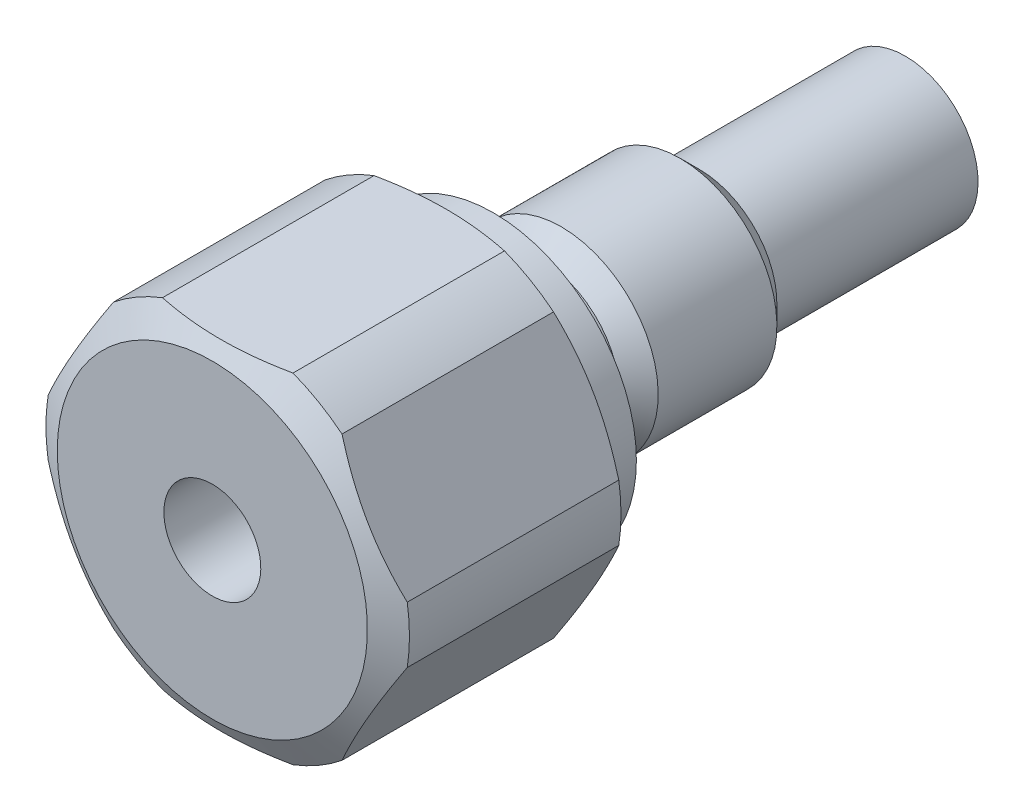
SolidWorks part; units mm, degrees
material "AISI 316 Annealed Stainless Steel Bar (SS)"
ref_plane "Front Plane" through (0, 0, 0) normal (0, 0, 1) x (1, 0, 0)
ref_plane "Top Plane" through (0, 0, 0) normal (0, 1, 0) x (1, 0, 0)
ref_plane "Right Plane" through (0, 0, 0) normal (1, 0, 0) x (0, 0, -1)
ref_axis "CENTER" through (0, 0, 55) along (0, 0, -1)
sketch "Sketch1" plane through (0, 0, 0) normal (1, 0, 0) x (0, 0, -1)
  line L0 (105.3808, 0) -> (-49894.6192, 0) construction
  line L1 (-55, 0) -> (55, 0) construction
  line L2 (0, 2) -> (0, 3)
  line L3 (0, 3) -> (-8.5, 3)
  line L4 (-17, 3.2) -> (-17, 5.9)
  line L5 (-17, 5.9) -> (-18.6, 5.9)
  line L6 (-18.6, 5.9) -> (-18.6, 7)
  line L7 (-18.6, 7) -> (-28.6, 7)
  line L8 (-28.6, 7) -> (-28.6, 2)
  line L9 (-28.6, 2) -> (0, 2)
  line L10 (-17, 3.2) -> (-15, 3.2)
  line L11 (-15, 3.2) -> (-14.2, 4)
  line L12 (-14.2, 4) -> (-9.3, 4)
  line L13 (-9.3, 4) -> (-8.5, 3.2)
  line L14 (-8.5, 3.2) -> (-8.5, 3)
  dimension "D1" = 4
  dimension "D2" = 1
  dimension "D3" = 11.8
  dimension "D4" = 8
  dimension "D5" = 6.4
  dimension "D6" = 8.5
  dimension "D7" = 45
  dimension "D8" = 2
  dimension "D9" = 1.6
  dimension "D10" = 14
  dimension "D11" = 10
  dimension "D12" = 17
revolve "Main Base" add sketch "Sketch1" angle 360 about L0
sketch "Sketch3" plane through (0, 0, 28.6) normal (0, 0, 1) x (1, 0, 0)
  line L1 (8.0829, 0) -> (4.0415, 7)
  line L2 (4.0415, 7) -> (-4.0415, 7)
  line L3 (-4.0415, 7) -> (-8.0829, 0)
  line L4 (-8.0829, 0) -> (-4.0415, -7)
  line L5 (-4.0415, -7) -> (4.0415, -7)
  line L6 (4.0415, -7) -> (8.0829, 0)
  circle A0 centre (0, 0) radius 7 construction
  circle A1 centre (0, 0) radius 7 construction
  circle A2 centre (0, 0) radius 2 construction
  circle A3 centre (0, 0) radius 2
extrude "Hex Head" add sketch "Sketch3" against normal up to surface (10 mm away) up to face at (0, 7, 18.6)
sketch "Sketch5" plane through (0, 0, 0) normal (0, 1, 0) x (1, 0, 0)
  line L0 (-6.4, -18.6) -> (-7.5, -19.2351)
  line L1 (-4.0415, -18.6) -> (-8.0829, -18.6) construction
  line L2 (-7.5, -19.2351) -> (-7.5, -27.9649)
  line L3 (-7.5, -27.9649) -> (-6.4, -28.6)
  line L4 (-4.0415, -28.6) -> (-8.0829, -28.6) construction
  line L5 (-6.4, -28.6) -> (-8.0829, -28.6)
  line L6 (-8.0829, -28.6) -> (-8.0829, -18.6)
  line L7 (-8.0829, -18.6) -> (-6.4, -18.6)
  line L8 (0, -20.5119) -> (0, -50020.5119) construction
  line L9 (0, -55) -> (0, 55) construction
  point P17 (-5.9714, -28.6)
  point P18 (0, 0)
  dimension "D1" = 30
  dimension "D2" = 15
  dimension "D3" = 0.5
  dimension "D4" = 30
revolve "Hex Trim" cut sketch "Sketch5" angle 360 about L8
